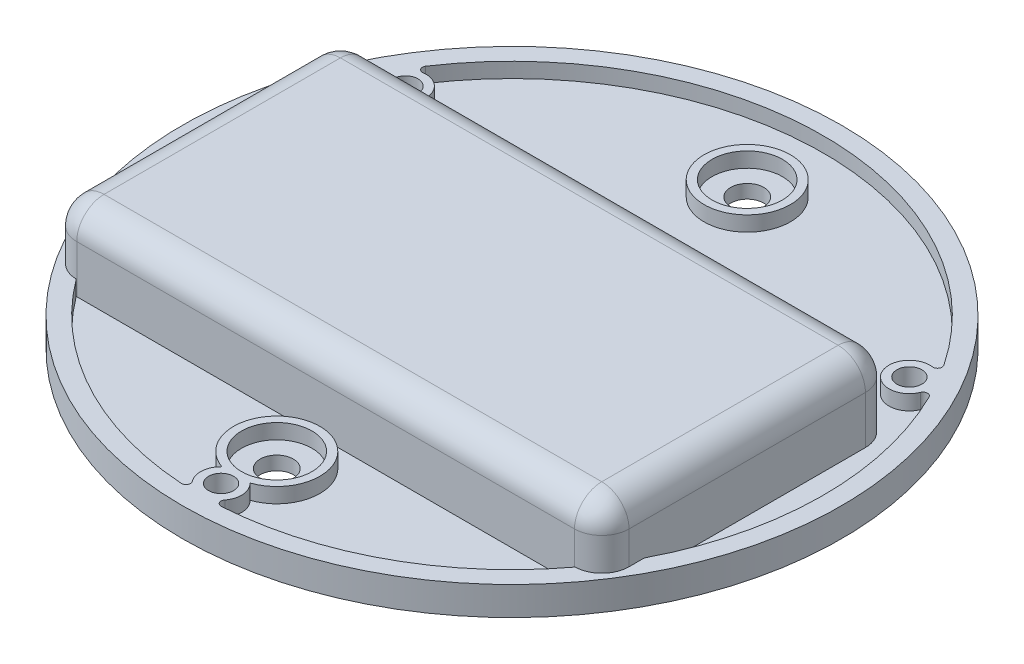
SolidWorks part; units mm, degrees
ref_plane "Plan de face" through (0, 0, 0) normal (0, 0, 1) x (1, 0, 0)
ref_plane "Plan de dessus" through (0, 0, 0) normal (0, 1, 0) x (1, 0, 0)
ref_plane "Plan de droite" through (0, 0, 0) normal (1, 0, 0) x (0, 0, -1)
sketch "Esquisse1" plane through (0, 0, 0) normal (0, 0, 1) x (1, 0, 0)
  line L0 (0, 0) -> (0, 36.7399) construction
  line L1 (0, 0) -> (-72.5, 0)
  line L2 (-72.5, 0) -> (-72.5, 6.3)
  line L3 (-72.5, 6.3) -> (-68.5, 6.3)
  line L4 (-68.5, 6.3) -> (-68.5, 3)
  line L5 (-68.5, 3) -> (0, 3)
  line L6 (0, 0) -> (0, 3)
  dimension "D1" = 6.3
  dimension "D2" = 3.3
  dimension "D3" = 145
  dimension "D4" = 137
revolve "Révolution1" add sketch "Esquisse1" angle 360 about L0
sketch "Esquisse2" plane through (0, 3, 0) normal (0, 1, 0) x (1, 0, 0)
  line L1 (-60.75, -41) -> (60.75, -41)
  line L2 (-60.75, -41) -> (-60.75, 23)
  line L3 (-60.75, 23) -> (60.75, 23)
  line L4 (60.75, -41) -> (60.75, 23)
  dimension "D1" = 64
  dimension "D2" = 121.5
  dimension "D3" = 60.75
  dimension "D4" = 41
extrude "Boss.-Extru.1" add sketch "Esquisse2" along normal blind 16.5
fillet "Congé1" radius 6 8 edges at (0, 19.5, -23) (60.75, 19.5, 9) (0, 19.5, 41) (-60.75, 19.5, 9) (60.75, 11.25, 41) (60.75, 11.25, -23) (-60.75, 11.25, -23) (-60.75, 11.25, 41)
sketch "Esquisse3" plane through (0, 6.3, 0) normal (0, 1, 0) x (1, 0, 0)
  line L0 (0, 0) -> (37.7485, 0) construction
  arc A0 (-3.0937, -60.7321) -> (3.0937, -60.7321) centre (0, -64) ccw
  arc A1 (-54.8758, -40.9987) -> (54.8758, -40.9987) centre (0, 0) ccw construction
  circle A2 centre (0, -51.75) radius 7.75
  arc A3 (3.0937, -60.7321) -> (-3.0937, -60.7321) centre (0, -51.75) ccw
  circle A4 centre (-55.4256, 32) radius 4.5
  circle A5 centre (55.4256, 32) radius 4.5
  circle A6 centre (0, 51.75) radius 9.5
  circle A7 centre (0, 51.75) radius 7.75
  dimension "D1" = 9
  dimension "D2" = 15.5
  dimension "D3" = 19
  dimension "D4" = 3
extrude "Boss.-Extru.4" add sketch "Esquisse3" against normal up to surface (3.3 mm away) separate body up to face at (0, 3, -19.8893)
sketch "Esquisse4" plane through (0, 6.3, 0) normal (0, 1, 0) x (1, 0, 0)
  arc A1 (-54.8758, -40.9987) -> (54.8758, -40.9987) centre (0, 0) ccw construction
  arc A3 (-4.4194, -68.3573) -> (4.4194, -68.3573) centre (0, 0) ccw
  arc A4 (4.4194, -68.3573) -> (3.563, -66.7486) centre (4.3548, -67.3594) cw
  arc A5 (-3.0937, -60.7321) -> (3.0937, -60.7321) centre (0, -64) ccw construction
  arc A6 (-3.563, -66.7486) -> (3.563, -66.7486) centre (0, -64) ccw
  arc A7 (-3.563, -66.7486) -> (-4.4194, -68.3573) centre (-4.3548, -67.3594) cw
  arc A8 (-56.0244, 36.46) -> (-56.9895, 38.0059) centre (-56.1575, 37.4511) cw
  arc A9 (-56.0244, 36.46) -> (-59.5875, 30.2886) centre (-55.4256, 32) ccw
  arc A10 (-56.9895, 38.0059) -> (-61.4088, 30.3514) centre (0, 0) ccw
  arc A11 (-61.4088, 30.3514) -> (-59.5875, 30.2886) centre (-60.5123, 29.9083) cw
  arc A12 (59.5875, 30.2886) -> (61.4088, 30.3514) centre (60.5123, 29.9083) cw
  arc A13 (59.5875, 30.2886) -> (56.0244, 36.46) centre (55.4256, 32) ccw
  arc A14 (61.4088, 30.3514) -> (56.9895, 38.0059) centre (0, 0) ccw
  arc A15 (56.9895, 38.0059) -> (56.0244, 36.46) centre (56.1575, 37.4511) cw
  arc M3 (-3.0937, -60.7321) -> (3.0937, -60.7321) centre (0, -64) ccw
  dimension "D1" = 1
  dimension "D2" = 1
  dimension "D3" = 3
extrude "Boss.-Extru.5" add sketch "Esquisse4" against normal up to surface (3.3 mm away) contours A8 A10 A9 | A10 A11 A9 | A14 A15 A13 | A12 A14 A13 | A7 A3 M3 | A3 A4 M3 up to face at (0, 3, -19.8893)
sketch "Esquisse5" plane through (0, 3, 0) normal (0, 1, 0) x (1, 0, 0)
  circle A0 centre (0, -51.75) radius 3.65
  circle A1 centre (0, 51.75) radius 3.65
  dimension "D1" = 7.3
  dimension "D2" = 7.3
extrude "Enlèv. mat.-Extru.1" cut sketch "Esquisse5" against normal blind 10
hole_wizard "Fraisage pour vis à tête fraisée M51" positions "Esquisse7" profile "Esquisse6" countersink size "M5" standard "ISO" end condition through all
sketch "Esquisse7" plane through (0, 0, 0) normal (0, -1, 0) x (1, 0, 0)
  point P0 (0, 64)
  point P1 (55.4256, -32)
  point P3 (-55.4256, -32)
sketch "Esquisse6" plane through (0, 0, 64) normal (1, 0, 0) x (0, 0, -1)
  line L0 (0, 0) -> (0, 19.5)
  line L1 (0, 19.5) -> (2.75, 19.5)
  line L2 (2.75, 19.5) -> (2.75, 2.45)
  line L3 (2.75, 2.45) -> (5.2, 0)
  line L5 (5.2, 0) -> (0, 0)
  line L6 (-2.75, 2.45) -> (-5.2, 0) construction
  line L11 (0, -6.35) -> (0, 107.95) construction
  dimension "Diamètre du perçage jusqu'au prochain" = 5.5
  dimension "Profondeur du perçage jusqu'au prochain" = 19.5
  dimension "Diamètre du fraisage entrant" = 10.4
  dimension "Angle du fraisage entrant" = 90
sketch "Esquisse8" plane through (0, 0, 0) normal (0, -1, 0) x (1, 0, 0)
  circle A0 centre (-46, -42.5) radius 6
  circle A1 centre (46, -42.5) radius 6
  circle A2 centre (10.9538, 61.6647) radius 6
  circle A3 centre (0, 64) radius 5.2 construction
  dimension "D1" = 12
  dimension "D2" = 12
  dimension "D6" = 12
  dimension "D3" = 92
  dimension "D4" = 46
  dimension "D5" = 42.5
  dimension "D7" = 62.63
extrude "Boss.-Extru.6" add sketch "Esquisse8" along normal blind 3.5 draft 14
